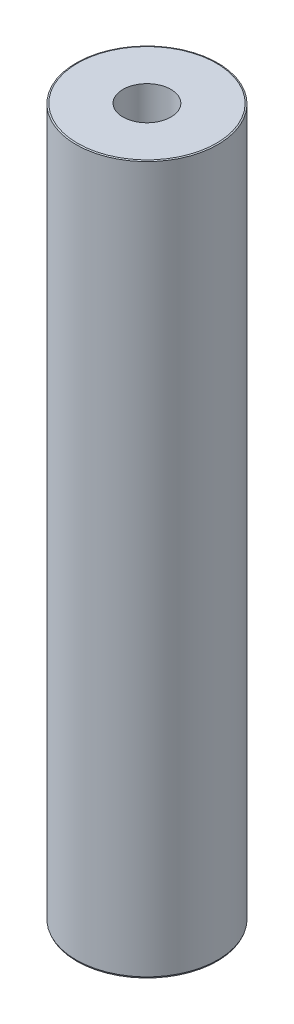
SolidWorks part; units mm, degrees
ref_plane "Front Plane" through (0, 0, 0) normal (0, 0, 1) x (1, 0, 0)
ref_plane "Top Plane" through (0, 0, 0) normal (0, 1, 0) x (1, 0, 0)
ref_plane "Right Plane" through (0, 0, 0) normal (1, 0, 0) x (0, 0, -1)
sketch "Sketch1" plane through (0, 0, 0) normal (0, 1, 0) x (1, 0, 0)
  circle A0 centre (0, 0) radius 60
  dimension "SHAFT_OD" = 120
extrude "Boss-Extrude1" add sketch "Sketch1" along normal blind 600
sketch "Sketch2" plane through (0, 0, 0) normal (0, 1, 0) x (1, 0, 0)
  circle A0 centre (0, 0) radius 20.3347
  dimension "BORE_D" = 40.6693
extrude "Cut-Extrude1" cut sketch "Sketch2" along normal through all
chamfer "Chamfer1" distance 0.427 angle 69.549 2 edges at (0, 600, 60) (0, 0, 60) first distance on face at (0, 600, 60) first distance on face at (0, 0, 20.3347)
